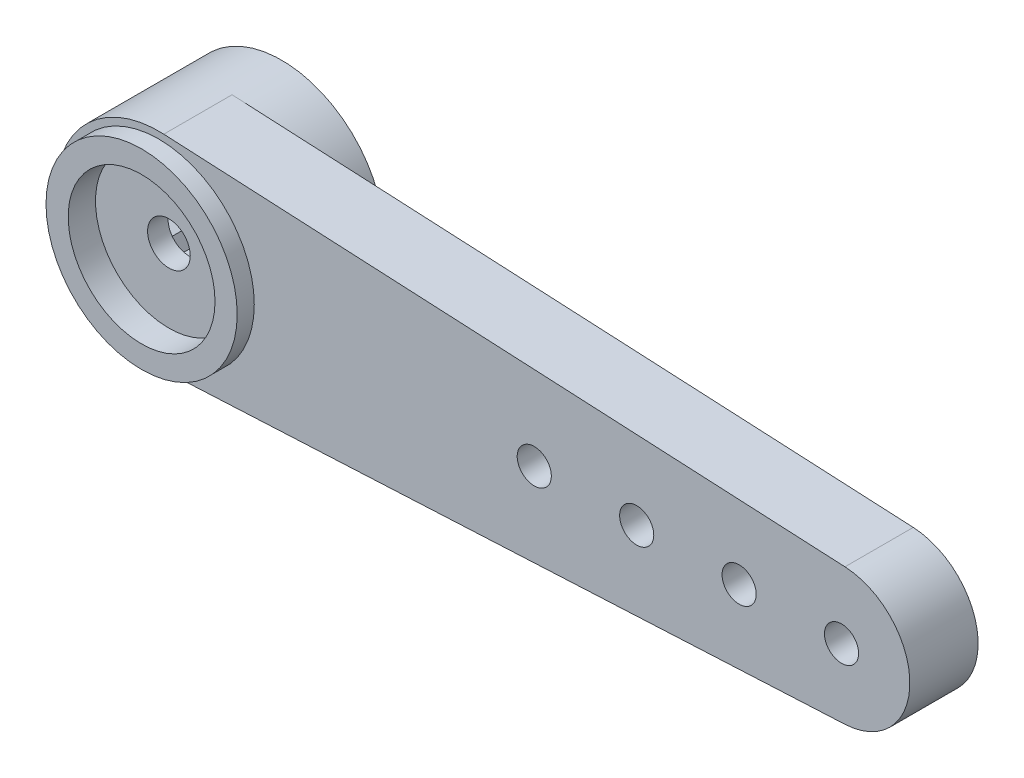
SolidWorks part; units mm, degrees
ref_plane "Front Plane" through (0, 0, 0) normal (0, 0, 1) x (1, 0, 0)
ref_plane "Top Plane" through (0, 0, 0) normal (0, 1, 0) x (1, 0, 0)
ref_plane "Right Plane" through (0, 0, 0) normal (1, 0, 0) x (0, 0, -1)
sketch "Sketch2" plane through (0, 0, 0) normal (0, 0, 1) x (1, 0, 0)
  line L0 (0, 0) -> (0, 4.5292) construction
  line L1 (0, 2) -> (0.3742, 1.7607)
  line L2 (2.6643, 5.984) -> (0, 0) construction
  line L3 (0.3742, 1.7607) -> (0.8135, 1.8271)
  line L4 (0.3742, 1.7607) -> (0.4158, 1.9563)
  line L33 (0.8135, 1.8271) -> (1.058, 1.4562)
  line L34 (1.058, 1.4562) -> (1.4863, 1.3383)
  line L35 (1.4863, 1.3383) -> (1.5588, 0.9)
  line L36 (1.5588, 0.9) -> (1.9021, 0.618)
  line L37 (1.9021, 0.618) -> (1.7901, 0.1882)
  line L38 (1.7901, 0.1882) -> (1.989, -0.2091)
  line L39 (1.989, -0.2091) -> (1.7119, -0.5562)
  line L40 (1.7119, -0.5562) -> (1.7321, -1)
  line L41 (1.7321, -1) -> (1.3377, -1.2044)
  line L42 (1.3377, -1.2044) -> (1.1756, -1.618)
  line L43 (1.1756, -1.618) -> (0.7321, -1.6444)
  line L44 (0.7321, -1.6444) -> (0.4158, -1.9563)
  line L45 (0.4158, -1.9563) -> (0, -1.8)
  line L46 (0, -1.8) -> (-0.4158, -1.9563)
  line L47 (-0.4158, -1.9563) -> (-0.7321, -1.6444)
  line L48 (-0.7321, -1.6444) -> (-1.1756, -1.618)
  line L49 (-1.1756, -1.618) -> (-1.3377, -1.2044)
  line L50 (-1.3377, -1.2044) -> (-1.7321, -1)
  line L51 (-1.7321, -1) -> (-1.7119, -0.5562)
  line L52 (-1.7119, -0.5562) -> (-1.989, -0.2091)
  line L53 (-1.989, -0.2091) -> (-1.7901, 0.1882)
  line L54 (-1.7901, 0.1882) -> (-1.9021, 0.618)
  line L55 (-1.9021, 0.618) -> (-1.5588, 0.9)
  line L56 (-1.5588, 0.9) -> (-1.4863, 1.3383)
  line L57 (-1.4863, 1.3383) -> (-1.058, 1.4562)
  line L58 (-1.058, 1.4562) -> (-0.8135, 1.8271)
  line L59 (-0.8135, 1.8271) -> (-0.3742, 1.7607)
  line L60 (-0.3742, 1.7607) -> (0, 2)
  line L61 (0.15, 2.9962) -> (20.1, 1.9975)
  line L62 (0.15, -2.9962) -> (20.1, -1.9975)
  circle A0 centre (0, 0) radius 2.8
  circle A1 centre (0, 0) radius 3
  circle A2 centre (0, 0) radius 2 construction
  circle A3 centre (0, 0) radius 0.625
  circle A4 centre (0, 0) radius 2.15
  circle A5 centre (20, 0) radius 2
  circle A6 centre (20, 0) radius 0.5
  circle A7 centre (17, 0) radius 0.5
  circle A8 centre (14, 0) radius 0.5
  circle A9 centre (11, 0) radius 0.5
  point P11 (0.8135, 1.8271)
  point P57 (0, 0)
  dimension "D1" = 6
  dimension "D2" = 5.6
  dimension "D3" = 4
  dimension "D7" = 1.25
  dimension "D9" = 4.3
  dimension "D10" = 4
  dimension "D12" = 1
  dimension "D4" = 24
  dimension "D5" = 12
  dimension "D6" = 0.2
  dimension "D11" = 20
  dimension "D13" = 3
  dimension "D14" = 3
  dimension "D15" = 3
  dimension "D8" = 15
extrude "Boss-Extrude1" add sketch "Sketch2" along normal blind 3.6 contours A1 A0 region at (2.1122, 2.0091, 0)
extrude "Boss-Extrude2" add sketch "Sketch2<3>" along normal blind 4.1 contours A4 | A0
sketch "Sketch2<3>" plane through (0, 0, 0) normal (0, 0, 1) x (1, 0, 0) same geometry as "Sketch2"
extrude "Boss-Extrude3" add sketch "Sketch2<4>" along normal blind 0.6 from offset 2.7 contours A4 L59 L60 L1 L3 L33 L34 L35 L36 L37 L38 L39 L40 L41 L42 L43 L44 L45 L46 L47 L48 L49 L50 L51 L52 L53 L54 L55 L56 L57 L58 | L60 L59 L58 L57 L56 L55 L54 L53 L52 L51 L50 L49 L48 L47 L46 L45 L44 L43 L42 L41 L40 L39 L38 L37 L36 L35 L34 L33 L3 L1 A3 region at (0.1569, 1.8331, 0) region at (-2.0892, 0, 0)
sketch "Sketch2<4>" plane through (0, 0, 0) normal (0, 0, 1) x (1, 0, 0) same geometry as "Sketch2"
extrude "Boss-Extrude4" add sketch "Sketch2<5>" along normal up to surface (2.7 mm away) contours A4 L59 L60 L1 L3 L33 L34 L35 L36 L37 L38 L39 L40 L41 L42 L43 L44 L45 L46 L47 L48 L49 L50 L51 L52 L53 L54 L55 L56 L57 L58 region at (-2.0892, 0, 0) up to face at (2.15, 0, 2.7)
sketch "Sketch2<5>" plane through (0, 0, 0) normal (0, 0, 1) x (1, 0, 0) same geometry as "Sketch2"
extrude "Boss-Extrude5" add sketch "Sketch2<6>" against normal blind 2 from surface contours A5 L61 A1 L62 | A5 A6 region at (9.8669, 0, 0) region at (21.4081, 1.3394, 0) starting at face at (2.8, 0, 3.6)
sketch "Sketch2<6>" plane through (0, 0, 0) normal (0, 0, 1) x (1, 0, 0) same geometry as "Sketch2"
